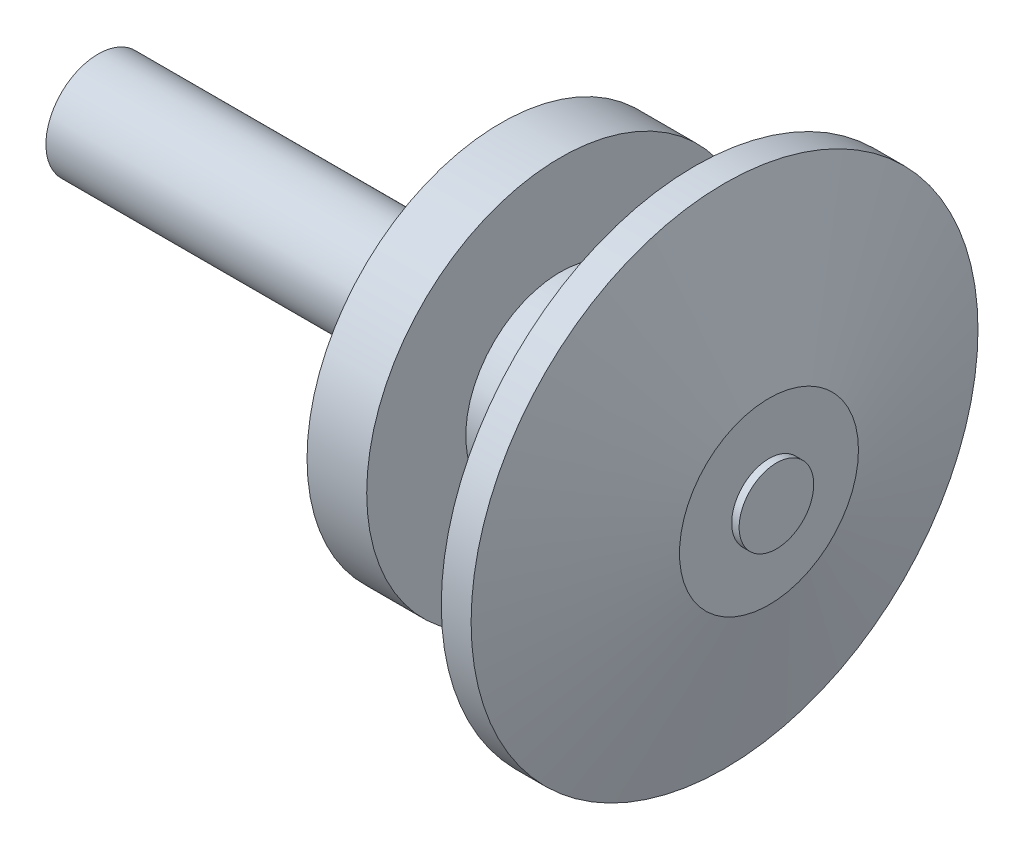
SolidWorks part; units mm, degrees
material "Delrin 150"
ref_plane "Front Plane" through (0, 0, 0) normal (0, 0, 1) x (1, 0, 0)
ref_plane "Top Plane" through (0, 0, 0) normal (0, 1, 0) x (1, 0, 0)
ref_plane "Right Plane" through (0, 0, 0) normal (1, 0, 0) x (0, 0, -1)
ref_axis "Axis1" through (0, 0, -88.99) along (0, 0, 1)
ref_axis "Axis2" through (0, -55, 0) along (0, 1, 0)
ref_axis "Axis3" through (-88.99, 0, 0) along (1, 0, 0)
sketch "Sketch1" plane through (0, 0, 0) normal (0, 0, 1) x (1, 0, 0)
  line L0 (-22.4892, 1.75) -> (-8.9892, 1.75)
  line L1 (-8.9892, 1.75) -> (-8.9892, 6.4963)
  line L2 (-8.9892, 6.4963) -> (-6.9892, 6.4963)
  line L3 (-6.9892, 6.4963) -> (-6.9892, 3.175)
  line L4 (-6.9892, 3.175) -> (-2.4892, 3.175)
  line L5 (-2.4892, 3.175) -> (-2.4892, 8.4963)
  line L6 (-2.4892, 8.4963) -> (-1.4892, 8.4963)
  line L7 (-1.4892, 8.4963) -> (0, 3)
  line L8 (0, 3) -> (0, 1.25)
  line L9 (0, 1.25) -> (0.25, 1.25)
  line L10 (0.25, 1.25) -> (0.25, 0)
  line L11 (0.25, 0) -> (-22.4892, 0)
  line L12 (-22.4892, 0) -> (-22.4892, 1.75)
  line L13 (-2.4892, 8.4963) -> (-30.48, 8.4963) construction
  line L14 (-22.4892, 0) -> (-30.48, 0) construction
  dimension "D1" = 0.25
  dimension "D2" = 1.25
  dimension "D3" = 8.4963
  dimension "D4" = 2.4892
  dimension "D5" = 4.5
  dimension "D6" = 27.9908
  dimension "D7" = 1
  dimension "D8" = 3
  dimension "D9" = 2
  dimension "D10" = 6.35
  dimension "D11" = 20
  dimension "D12" = 3.5
  dimension "D13" = 2
revolve "Revolve1" add sketch "Sketch1" angle 360 about L14
